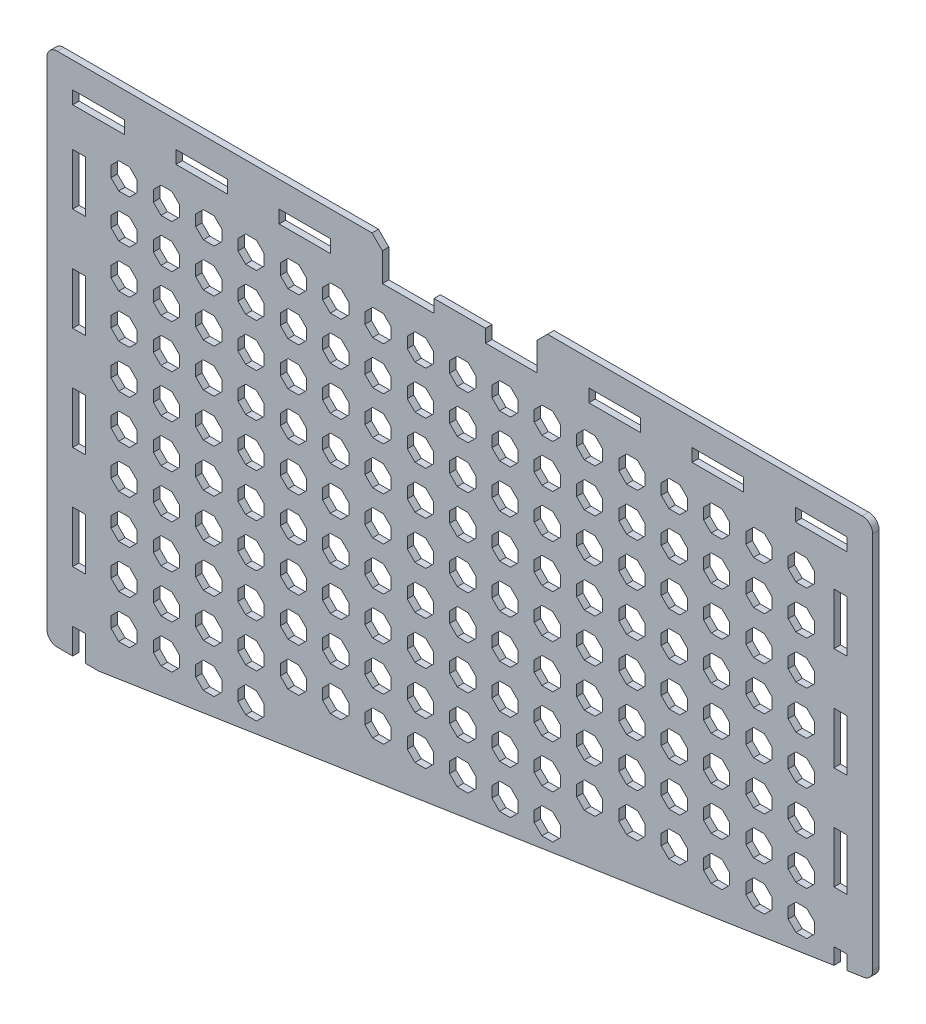
SolidWorks part; units mm, degrees
material "Oak"
ref_plane "Front Plane" through (0, 0, 0) normal (0, 0, 1) x (1, 0, 0)
ref_plane "Top Plane" through (0, 0, 0) normal (0, 1, 0) x (1, 0, 0)
ref_plane "Right Plane" through (0, 0, 0) normal (1, 0, 0) x (0, 0, -1)
sketch "Sketch1" plane through (0, 0, 0) normal (0, 0, 1) x (1, 0, 0)
  line L1 (0, 0) -> (203.2, 0)
  line L2 (0, 0) -> (0, -127)
  line L3 (0, -127) -> (203.2, -127)
  line L4 (203.2, 0) -> (203.2, -127)
extrude "Boss-Extrude1" add sketch "Sketch1" along normal blind 1.5875
sketch "Sketch2" plane through (0, 0, 1.5875) normal (0, 0, 1) x (1, 0, 0)
  line L0 (12.7, -127) -> (203.2, -127)
  line L1 (203.2, -127) -> (203.2, -97.79)
  line L2 (203.2, -127) -> (203.2, 0) construction
  line L3 (203.2, -97.79) -> (12.7, -127)
  line L4 (0, -127) -> (203.2, -127) construction
extrude "Cut-Extrude1" cut sketch "Sketch2" against normal through all
sketch "Sketch3" plane through (0, 0, 1.5875) normal (0, 0, 1) x (1, 0, 0)
  line L1 (6.35, -6.35) -> (19.05, -6.35)
  line L2 (6.35, -6.35) -> (6.35, -9.525)
  line L3 (6.35, -9.525) -> (19.05, -9.525)
  line L4 (19.05, -6.35) -> (19.05, -9.525)
extrude "Cut-Extrude2" cut sketch "Sketch3" against normal through all
pattern_linear "LPattern1" count 8 spacing 25.4 along (1, 0, 0) of "Cut-Extrude2"
sketch "Sketch4" plane through (0, 0, 1.5875) normal (0, 0, 1) x (1, 0, 0)
  line L1 (6.35, -19.05) -> (9.525, -19.05)
  line L2 (6.35, -19.05) -> (6.35, -31.75)
  line L3 (6.35, -31.75) -> (9.525, -31.75)
  line L4 (9.525, -19.05) -> (9.525, -31.75)
extrude "Cut-Extrude3" cut sketch "Sketch4" against normal through all
pattern_linear "LPattern2" count 5 spacing 25.4 along (0, -1, 0) of "Cut-Extrude3"
sketch "Sketch5" plane through (0, 0, 1.5875) normal (0, 0, 1) x (1, 0, 0)
  line L1 (196.85, -19.05) -> (193.675, -19.05)
  line L2 (196.85, -19.05) -> (196.85, -31.75)
  line L3 (196.85, -31.75) -> (193.675, -31.75)
  line L4 (193.675, -19.05) -> (193.675, -31.75)
extrude "Cut-Extrude4" cut sketch "Sketch5" against normal through all
pattern_linear "LPattern3" count 4 spacing 25.4 along (0, -1, 0) of "Cut-Extrude4"
fillet "Fillet1" radius 2.54 4 edges at (203.2, -97.79, 0.7937) (203.2, 0, 0.7937) (0, 0, 0.7937) (0, -127, 0.7937)
hole_wizard "Hole1" [suppressed] positions "Sketch7" profile "Sketch6" legacy
sketch "Sketch7" plane through (0, 0, 1.5875) normal (0, 0, 1) x (1, 0, 0)
  point P0 (19.05, -19.05)
sketch "Sketch6" plane through (19.05, -19.05, 1.5875) normal (1, 0, 0) x (0, -1, 0)
  line L0 (0, 0) -> (0, 1.5875)
  line L1 (0, 1.5875) -> (2.54, 1.5875)
  line L2 (2.54, 1.5875) -> (2.54, 0)
  line L3 (2.54, 0) -> (0, 0)
  line L4 (0, 110) -> (0, -10) construction
  dimension "Diameter" = 5.08
  dimension "Depth" = 1.5875
pattern_linear "LPattern4" [suppressed] count 14 spacing 12.7 count 9 spacing 12.7
sketch "Sketch8" plane through (0, 0, 1.5875) normal (0, 0, 1) x (1, 0, 0)
  line L0 (200.66, 0) -> (2.54, 0) construction
  line L1 (82.55, 0) -> (120.65, 0)
  line L2 (82.55, 0) -> (82.55, -6.35)
  line L3 (82.55, -6.35) -> (120.65, -6.35)
  line L4 (120.65, 0) -> (120.65, -6.35)
  line L5 (95.25, -6.35) -> (82.55, -6.35) construction
extrude "Cut-Extrude5" cut sketch "Sketch8" against normal through all
chamfer "Chamfer1" distance 2.54 angle 45 2 edges at (120.65, 0, 0.7937) (82.55, 0, 0.7937)
sketch "Sketch9" plane through (0, 0, 1.5875) normal (0, 0, 1) x (1, 0, 0)
  line L0 (15.784, -20.3369) -> (17.6699, -22.2227)
  line L1 (20.3369, -22.2227) -> (22.2227, -20.3369)
  line L2 (22.2227, -20.3369) -> (22.2227, -17.6699)
  line L3 (22.2227, -17.6699) -> (20.3369, -15.784)
  line L4 (20.3369, -15.784) -> (17.6699, -15.784)
  line L5 (17.6699, -15.784) -> (15.784, -17.6699)
  line L6 (15.784, -17.6699) -> (15.784, -20.3369)
  line L7 (17.6699, -22.2227) -> (20.3369, -22.2227)
  circle A0 centre (19.0034, -19.0034) radius 3.4846 construction
extrude "Cut-Extrude6" cut sketch "Sketch9" against normal through all
pattern_linear "LPattern5" count 17 spacing 10.414 along (1, 0, 0) count 10 spacing 10.668 along (0, -1, 0) skipping (4, 9), (5, 9), (6, 9), (7, 9), (8, 9), (9, 9), (10, 9), (11, 8), (11, 9), (12, 8), (12, 9), (13, 8), (13, 9), (14, 8), (14, 9), (15, 8), (15, 9), (16, 8), (16, 9) of "Cut-Extrude6"
